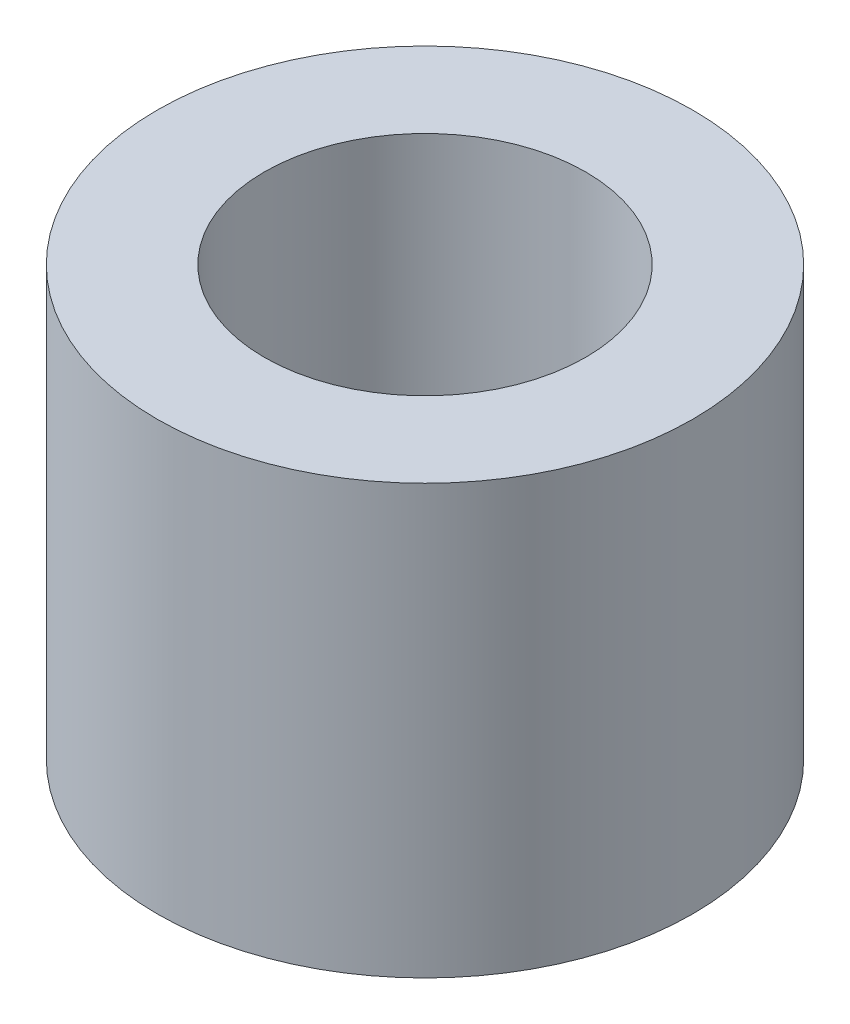
SolidWorks part; units mm, degrees
material "Brass"
ref_plane "Front Plane" through (0, 0, 0) normal (0, 0, 1) x (1, 0, 0)
ref_plane "Top Plane" through (0, 0, 0) normal (0, 1, 0) x (1, 0, 0)
ref_plane "Right Plane" through (0, 0, 0) normal (1, 0, 0) x (0, 0, -1)
sketch "Sketch1" plane through (0, 0, 0) normal (0, 1, 0) x (1, 0, 0)
  circle A0 centre (0, 0) radius 1.5
  circle A1 centre (0, 0) radius 2.5
  dimension "D1" = 5
  dimension "D2" = 3
extrude "Boss-Extrude1" add sketch "Sketch1" along normal mid plane 4
